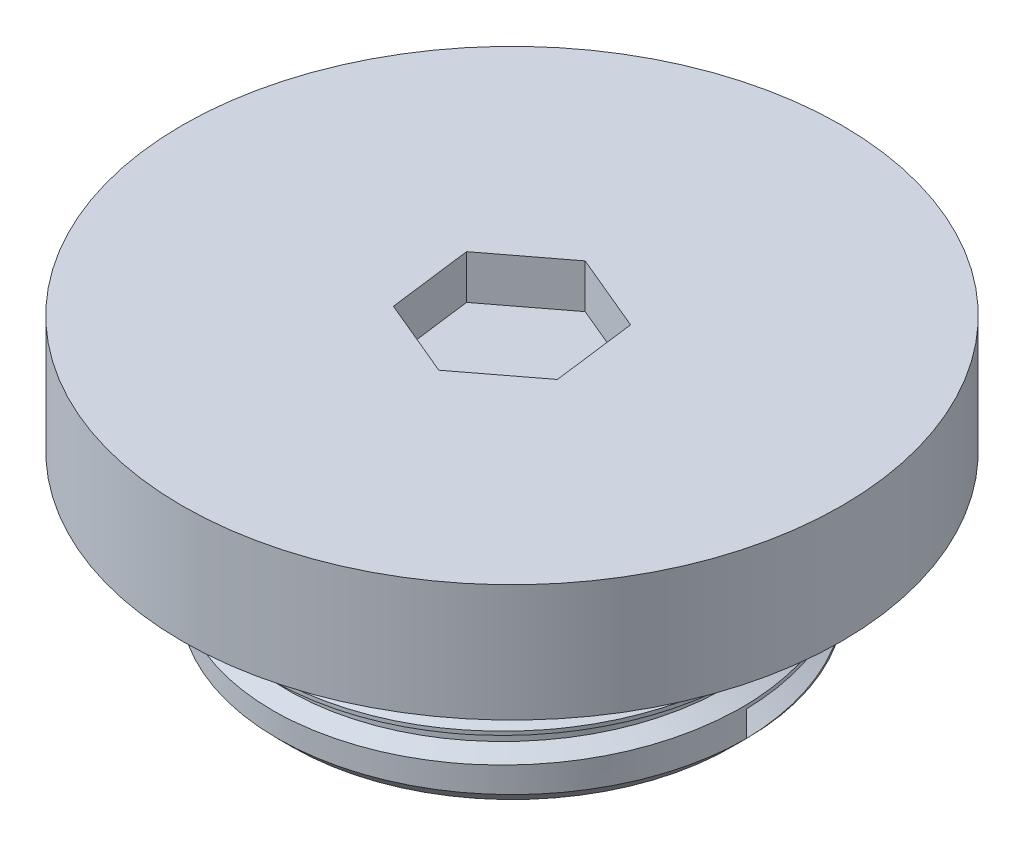
SolidWorks part; units mm, degrees
material "7075-T6 (SN)"
ref_plane "Front Plane" through (0, 0, 0) normal (0, 0, 1) x (1, 0, 0)
ref_plane "Top Plane" through (0, 0, 0) normal (0, 1, 0) x (1, 0, 0)
ref_plane "Right Plane" through (0, 0, 0) normal (1, 0, 0) x (0, 0, -1)
sketch "Sketch1" plane through (0, 0, 0) normal (0, 1, 0) x (1, 0, 0)
  circle A0 centre (0, 0) radius 16
  dimension "D1" = 32
extrude "Boss-Extrude1" add sketch "Sketch1" along normal blind 10
sketch "Sketch2" plane through (0, 10, 0) normal (0, 1, 0) x (1, 0, 0)
  circle A0 centre (0, 0) radius 22.5
  dimension "D1" = 45
extrude "Boss-Extrude2" add sketch "Sketch2" along normal blind 8 contours A0
chamfer "Chamfer1" distance 1 angle 45 1 edges at (0, 0, 16)
sketch "Sketch3" plane through (0, 0, 0) normal (0, -1, 0) x (1, 0, 0)
  circle A0 centre (0, 0) radius 10
  dimension "D1" = 20
extrude "Cut-Extrude1" cut sketch "Sketch3" against normal up to surface (10 mm away) up to face at (0, 10, 16)
sketch "Sketch4" plane through (0, 18, 0) normal (0, 1, 0) x (1, 0, 0)
  line L1 (5.3262, -2.2282) -> (4.5928, 3.4985)
  line L2 (4.5928, 3.4985) -> (-0.7334, 5.7267)
  line L3 (-0.7334, 5.7267) -> (-5.3262, 2.2282)
  line L4 (-5.3262, 2.2282) -> (-4.5928, -3.4985)
  line L5 (-4.5928, -3.4985) -> (0.7334, -5.7267)
  line L6 (0.7334, -5.7267) -> (5.3262, -2.2282)
  circle A1 centre (0, 0) radius 5 construction
  dimension "D1" = 10
extrude "Cut-Extrude2" cut sketch "Sketch4" against normal blind 3
chamfer "Chamfer2" distance 1 angle 45 1 edges at (0, 0, -10)
thread "Thread1" pitch 2 method cut profile "Thread Profile1" start angle 0, offset 0, length 0, pitch 2, diameter 32
ref_plane "Plane1" through (16, 1, 0) normal (0, 0, 1) x (1, 0, 0)
sketch "Thread Profile1" plane through (16, 1, 0) normal (0, 0, 1) x (1, 0, 0)
  line L0 (0, 0) -> (0, 2) construction
  line L11 (0, 0) -> (0, 1.75)
  line L12 (0, 1.75) -> (-1.0825, 1.125)
  line L13 (-1.0825, 1.125) -> (-1.0825, 0.625)
  line L15 (-1.0825, 0.625) -> (0, 0)
  line L17 (-1.0825, 0.875) -> (0, 0.875) construction
  point P2 (0, 0)
  dimension "Pitch" = 2
  dimension "Profile_Angle" = 60
  dimension "Profile_Land" = 0.5
  dimension "Profile_Height" = 1.0825
